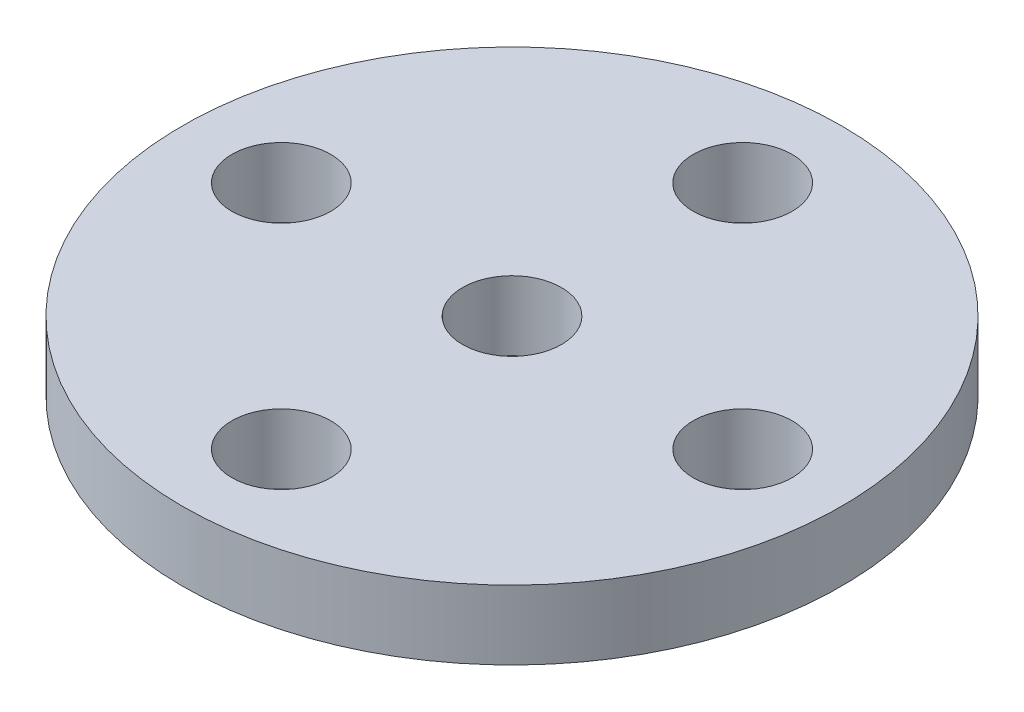
SolidWorks part; units mm, degrees
ref_plane "前视基准面" through (0, 0, 0) normal (0, 0, 1) x (1, 0, 0)
ref_plane "上视基准面" through (0, 0, 0) normal (0, 1, 0) x (1, 0, 0)
ref_plane "右视基准面" through (0, 0, 0) normal (1, 0, 0) x (0, 0, -1)
sketch "Sketch1" plane through (0, 0, 0) normal (0, 1, 0) x (1, 0, 0)
  circle A0 centre (0, 0) radius 10
  circle A1 centre (0, 0) radius 1.5
  circle A2 centre (0, 7) radius 1.5
  circle A3 centre (7, 0) radius 1.5
  circle A4 centre (0, -7) radius 1.5
  circle A5 centre (-7, 0) radius 1.5
  point P15 (-0.0502, 0.0495)
  point P17 (0, 0)
  dimension "D1" = 20
  dimension "D2" = 3
  dimension "D3" = 3
  dimension "D5" = 4
  dimension "D4" = 7
extrude "Boss-Extrude1" add sketch "Sketch1" along normal blind 2.1
ref_axis "Axis7" through (0, 2.1, 0) along (0, -1, 0)
